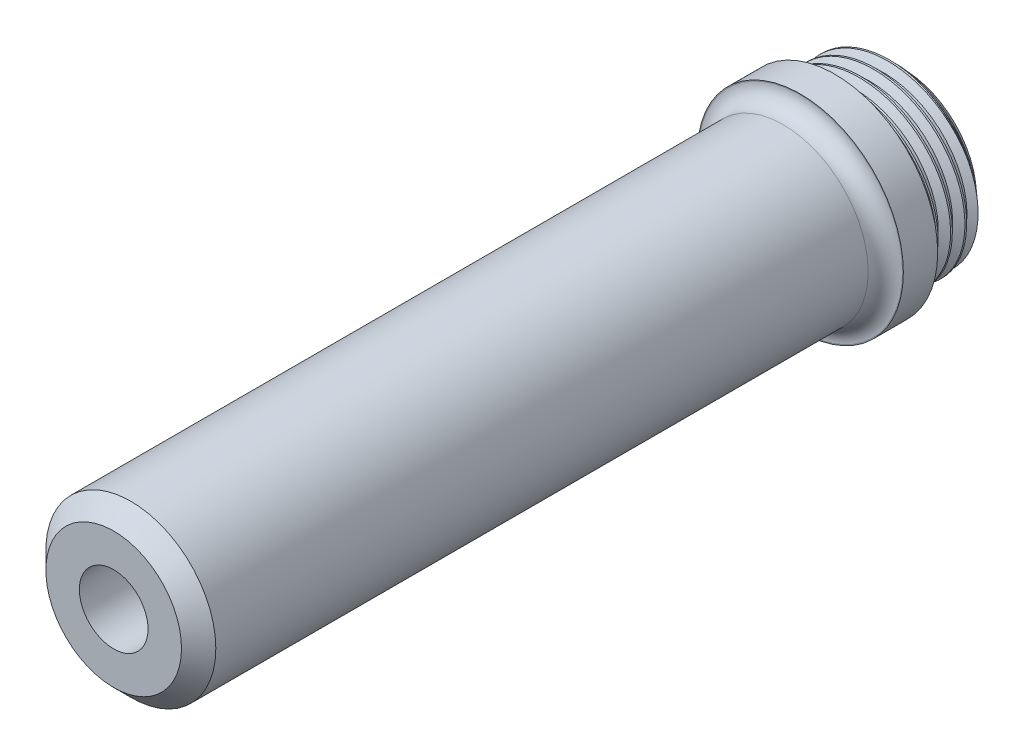
SolidWorks part; units mm, degrees
material "Plain Carbon Steel"
ref_plane "Front Plane" through (0, 0, 0) normal (0, 0, 1) x (1, 0, 0)
ref_plane "Top Plane" through (0, 0, 0) normal (0, 1, 0) x (1, 0, 0)
ref_plane "Right Plane" through (0, 0, 0) normal (1, 0, 0) x (0, 0, -1)
sketch "Sketch1" plane through (0, 0, 0) normal (0, 0, 1) x (1, 0, 0)
  circle A0 centre (0, 0) radius 7.62
  dimension "D1" = 15.24
extrude "Boss-Extrude1" add sketch "Sketch1" along normal blind 2.54
sketch "Sketch2" plane through (0, 0, 0) normal (0, 0, -1) x (-1, 0, 0)
  circle A0 centre (0, 0) radius 6.6675
  dimension "D1" = 13.335
extrude "Boss-Extrude2" add sketch "Sketch2" along normal blind 5.08
sketch "Sketch8" plane through (0, 0, 2.54) normal (0, 0, 1) x (1, 0, 0)
  circle A0 centre (0, 0) radius 6.2865
  dimension "D1" = 12.573
extrude "Boss-Extrude3" add sketch "Sketch8" along normal blind 50.8
thread "Thread1" pitch 1.0583 method cut profile "Thread Profile1" start angle 0, offset 0, length 5.461, pitch 1.0583, diameter 13.335
ref_plane "Plane1" through (6.6675, 0, -5.08) normal (0, -1, 0) x (1, 0, 0)
sketch "Thread Profile1" plane through (6.6675, 0, -5.08) normal (0, -1, 0) x (1, 0, 0)
  line L0 (0, 0) -> (0, 1.0583) construction
  line L11 (0, 0) -> (0, 0.926)
  line L12 (0, 0.926) -> (-0.5728, 0.5953)
  line L13 (-0.5728, 0.5953) -> (-0.5728, 0.3307)
  line L15 (-0.5728, 0.3307) -> (0, 0)
  line L17 (-0.5728, 0.463) -> (0, 0.463) construction
  point P2 (0, 0)
  dimension "Pitch" = 1.0583
  dimension "Profile_Angle" = 60
  dimension "Profile_Land" = 0.2646
  dimension "Profile_Height" = 0.5728
sketch "Sketch6" plane through (0, 0, 0) normal (0, 1, 0) x (1, 0, 0)
  line L0 (0, 0) -> (0, 5.08) construction
  line L1 (6.6675, 5.08) -> (-6.6675, 5.08) construction
  line L2 (4.699, 5.715) -> (7.239, 3.429)
  line L3 (7.239, 3.429) -> (7.239, 5.715)
  line L4 (7.239, 5.715) -> (4.699, 5.715)
  dimension "D1" = 4.699
  dimension "D2" = 2.54
  dimension "D3" = 2.286
  dimension "D4" = 0.635
revolve "Cut-Revolve1" cut sketch "Sketch6" angle 360 about L0
chamfer "Chamfer1" distance 1.27 angle 45 1 edges at (6.2865, 0, 53.34)
sketch "Sketch7" plane through (0, 0, 53.34) normal (0, 0, 1) x (1, 0, 0)
  circle A1 centre (0, 0) radius 2.54
  dimension "D1" = 5.08
extrude "Cut-Extrude1" cut sketch "Sketch7" against normal through all draft 2.25 draft outward yes
fillet "Fillet1" radius 1.27 1 edges at (6.2865, 0, 2.54)
